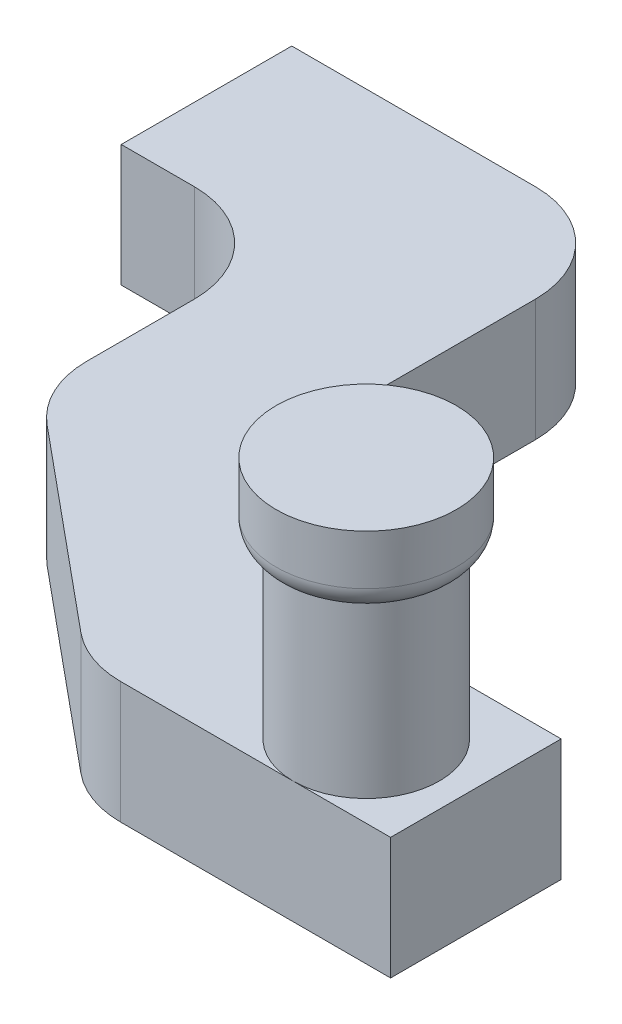
SolidWorks part; units mm, degrees
ref_plane "Front Plane" through (0, 0, 0) normal (0, 0, 1) x (1, 0, 0)
ref_plane "Top Plane" through (0, 0, 0) normal (0, 1, 0) x (1, 0, 0)
ref_plane "Right Plane" through (0, 0, 0) normal (1, 0, 0) x (0, 0, -1)
sketch "Sketch1" plane through (0, 0, 0) normal (0, 1, 0) x (1, 0, 0)
  line L0 (0, 0) -> (7, 0)
  line L1 (7, 0) -> (7, -7)
  line L2 (7, -7) -> (10.0804, -9.5517)
  line L3 (10.0804, -9.5517) -> (15.0804, -9.5517)
  line L4 (0, -3.5) -> (3.5, -3.5)
  line L5 (3.5, -3.5) -> (3.5, -8.6456)
  line L6 (3.5, -8.6456) -> (8.8191, -13.0517)
  line L7 (8.8191, -13.0517) -> (15.0804, -13.0517)
  line L8 (15.0804, -9.5517) -> (15.0804, -13.0517)
  line L9 (0, 0) -> (0, -3.5)
  point P11 (7, -7)
  dimension "D1" = 7
  dimension "D2" = 7
  dimension "D3" = 4
  dimension "D4" = 5
  dimension "D5" = 3.5
extrude "Boss-Extrude1" add sketch "Sketch1" along normal blind 2.5
fillet "Fillet1" radius 2 5 edges at (7, 1.25, 7) (3.5, 1.25, 8.6456) (3.5, 1.25, 3.5) (7, 1.25, 0) (8.8191, 1.25, 13.0517)
sketch "Sketch2" plane through (0, 2.5, 0) normal (0, 1, 0) x (1, 0, 0)
  line L0 (15.0804, -9.5517) -> (10.0804, -9.5517) construction
  line L1 (15.0804, -13.0517) -> (15.0804, -9.5517) construction
  circle A0 centre (13.0804, -11.5517) radius 1.5
  dimension "D1" = 2
  dimension "D2" = 2
extrude "Boss-Extrude2" add sketch "Sketch2" along normal blind 3.5
sketch "Sketch3" plane through (0, 6, 0) normal (0, 1, 0) x (1, 0, 0)
  circle A0 centre (13.0804, -11.5517) radius 1.85
extrude "Boss-Extrude3" add sketch "Sketch3" along normal blind 1.5
fillet "Fillet2" radius 0.5 1 edges at (13.0804, 6, 13.4017)
sketch "Sketch4" plane through (0, 0, 0) normal (0, -1, 0) x (-1, 0, 0)
  circle A0 centre (-1.5563, -1.4668) radius 1.5
extrude "Boss-Extrude4" add sketch "Sketch4" along normal blind 3
sketch "Sketch5" plane through (0, -3, 0) normal (0, -1, 0) x (1, 0, 0)
  circle A0 centre (1.5536, 1.4529) radius 1.72
extrude "Boss-Extrude5" add sketch "Sketch5" along normal blind 1
fillet "Fillet3" radius 0.5 1 edges at (1.5536, -3, -0.2671)
